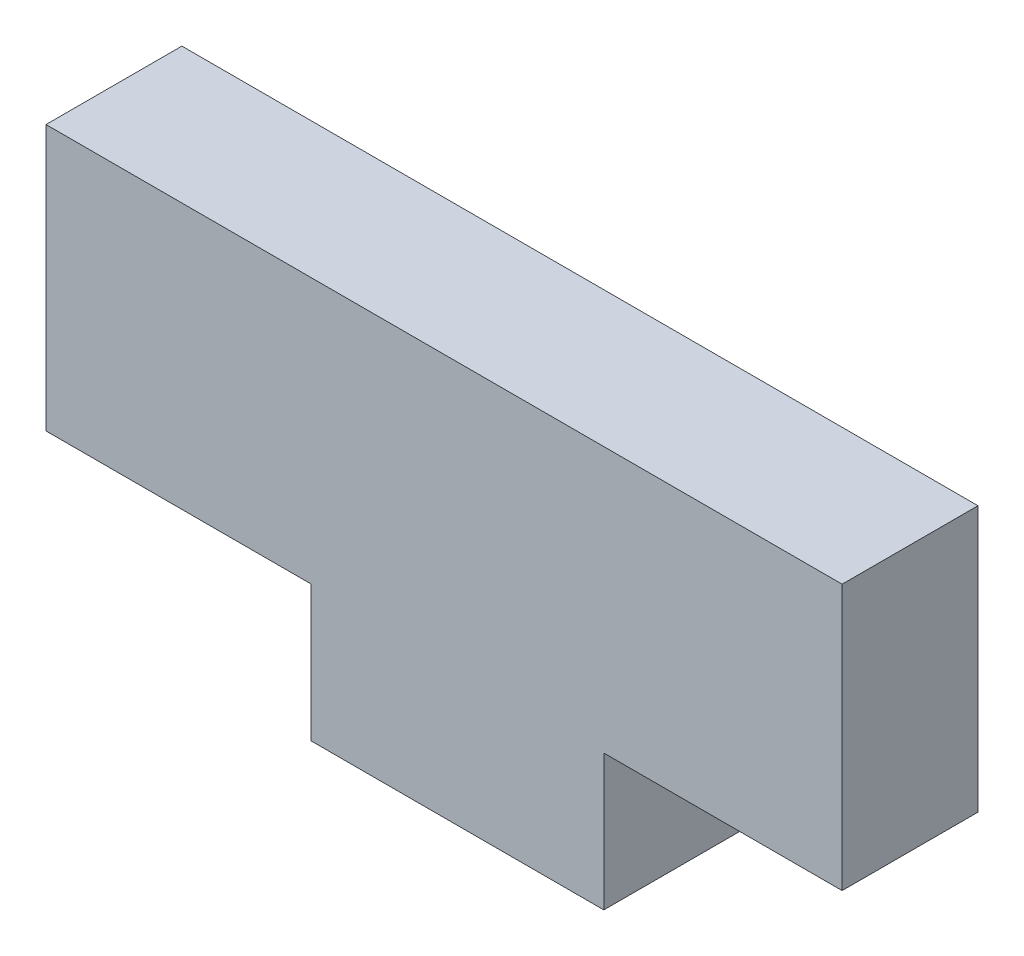
SolidWorks part; units mm, degrees
ref_plane "Front Plane" through (0, 0, 0) normal (0, 0, 1) x (1, 0, 0)
ref_plane "Top Plane" through (0, 0, 0) normal (0, 1, 0) x (1, 0, 0)
ref_plane "Right Plane" through (0, 0, 0) normal (1, 0, 0) x (0, 0, -1)
sketch "Sketch1" plane through (0, 0, 0) normal (0, 0, 1) x (1, 0, 0)
  line L0 (21.0202, 0) -> (30, 0)
  line L1 (0, 0) -> (9.9773, 0)
  line L2 (0, 0) -> (0, 10)
  line L3 (0, 10) -> (30, 10)
  line L4 (30, 0) -> (30, 10)
  line L6 (9.9773, 0) -> (9.9773, -5.12)
  line L7 (9.9773, -5.12) -> (21.0202, -5.12)
  line L8 (21.0202, 0) -> (21.0202, -5.12)
  dimension "D1" = 10
  dimension "D2" = 30
  dimension "D3" = 5.12
extrude "Boss-Extrude1" add sketch "Sketch1" along normal blind 5.12
equation "\"D3@Sketch1\" = \"mdf@fmv1.assembly\""
equation "\"D1@Boss-Extrude1\"=\"mdf@fmv1.assembly\""
